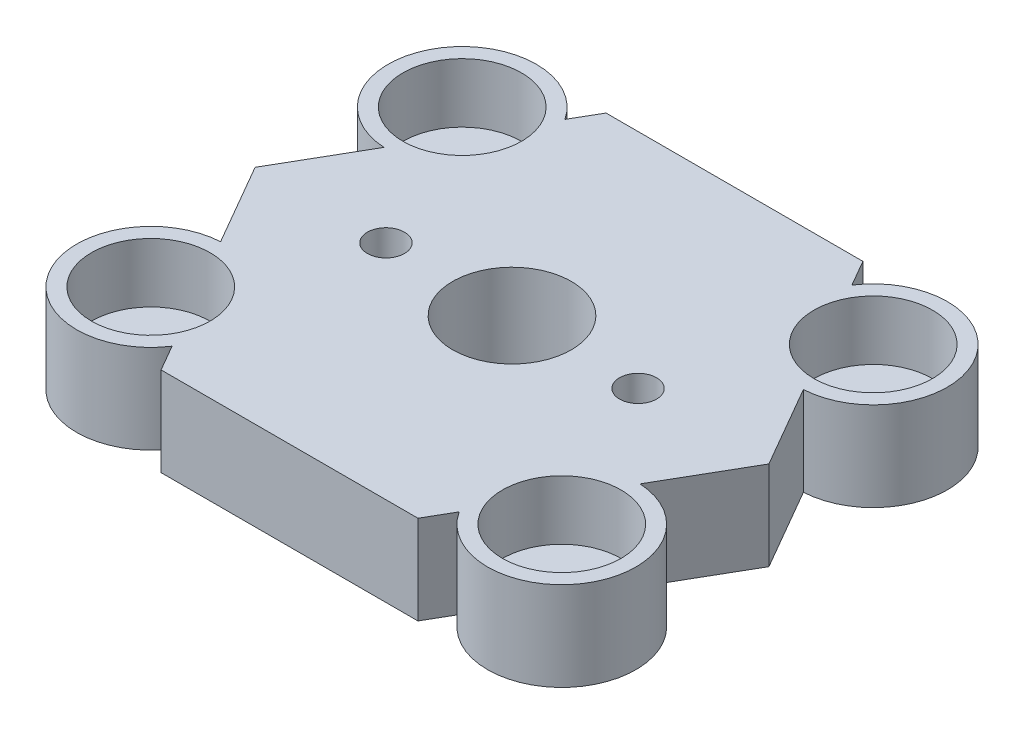
SolidWorks part; units mm, degrees
ref_plane "Front Plane" through (0, 0, 0) normal (0, 0, 1) x (1, 0, 0)
ref_plane "Top Plane" through (0, 0, 0) normal (0, 1, 0) x (1, 0, 0)
ref_plane "Right Plane" through (0, 0, 0) normal (1, 0, 0) x (0, 0, -1)
sketch "Sketch2" plane through (0, 0, 0) normal (0, 1, 0) x (1, 0, 0)
  line L0 (-8.5, 0) -> (8.5, 0) construction
  line L1 (0, 20.1846) -> (0, -20.1846) construction
  line L2 (-13.8564, 6) -> (-13.8564, 15) construction
  line L3 (17.3205, 0) -> (8.6603, 15)
  line L4 (8.6603, 15) -> (-8.6603, 15)
  line L5 (-8.6603, 15) -> (-17.3205, 0)
  line L6 (-17.3205, 0) -> (-8.6603, -15)
  line L7 (-8.6603, -15) -> (8.6603, -15)
  line L8 (8.6603, -15) -> (17.3205, 0)
  line L9 (-8.6603, 15) -> (-13.8564, 15) construction
  circle A0 centre (0, 0) radius 4
  circle A1 centre (8.5, 0) radius 1.25
  circle A2 centre (-8.5, 0) radius 1.25
  circle A3 centre (0, 0) radius 15 construction
  circle A4 centre (-13.8564, 10.5) radius 5
  circle A5 centre (-13.8564, 10.5) radius 1.5
  circle A6 centre (13.8564, 10.5) radius 1.5
  circle A7 centre (13.8564, 10.5) radius 5
  circle A8 centre (13.8564, -10.5) radius 1.5
  circle A9 centre (13.8564, -10.5) radius 5
  circle A10 centre (-13.8564, -10.5) radius 5
  circle A11 centre (-13.8564, -10.5) radius 1.5
  point P7 (0, 0)
  point P8 (0, 0)
  point P32 (-12.9904, 11.25)
  point P33 (0, 0)
  dimension "D1" = 8
  dimension "D3" = 2.5
  dimension "D4" = 2.5
  dimension "D6" = 10
  dimension "D7" = 3
  dimension "D2" = 17
  dimension "D5" = 30
  dimension "D8" = 9
extrude "Boss-Extrude1" add sketch "Sketch2" along normal blind 6 contours A4 | L3 L4 L5 L6 L7 L8 | A10 | A9 | A7 | A6 | A5 | A0 | A1 | A2 | A11 | A8
sketch "Sketch3" plane through (0, 0, 0) normal (0, -1, 0) x (1, 0, 0)
  circle A0 centre (-8.5, 0) radius 3.5
  circle A1 centre (8.5, 0) radius 3.5
  dimension "D1" = 7
  dimension "D2" = 7
extrude "Cut-Extrude3" cut sketch "Sketch3" against normal blind 3 contours A0 | A1
sketch "Sketch4" plane through (0, 6, 0) normal (0, 1, 0) x (1, 0, 0)
  circle A0 centre (-13.8564, 10.5) radius 4
  circle A1 centre (13.8564, 10.5) radius 4
  circle A2 centre (-13.8564, -10.5) radius 4
  circle A3 centre (13.8564, -10.5) radius 4
  dimension "D1" = 8
  dimension "D2" = 8
  dimension "D3" = 8
  dimension "D4" = 8
extrude "Cut-Extrude4" cut sketch "Sketch4" against normal blind 4
